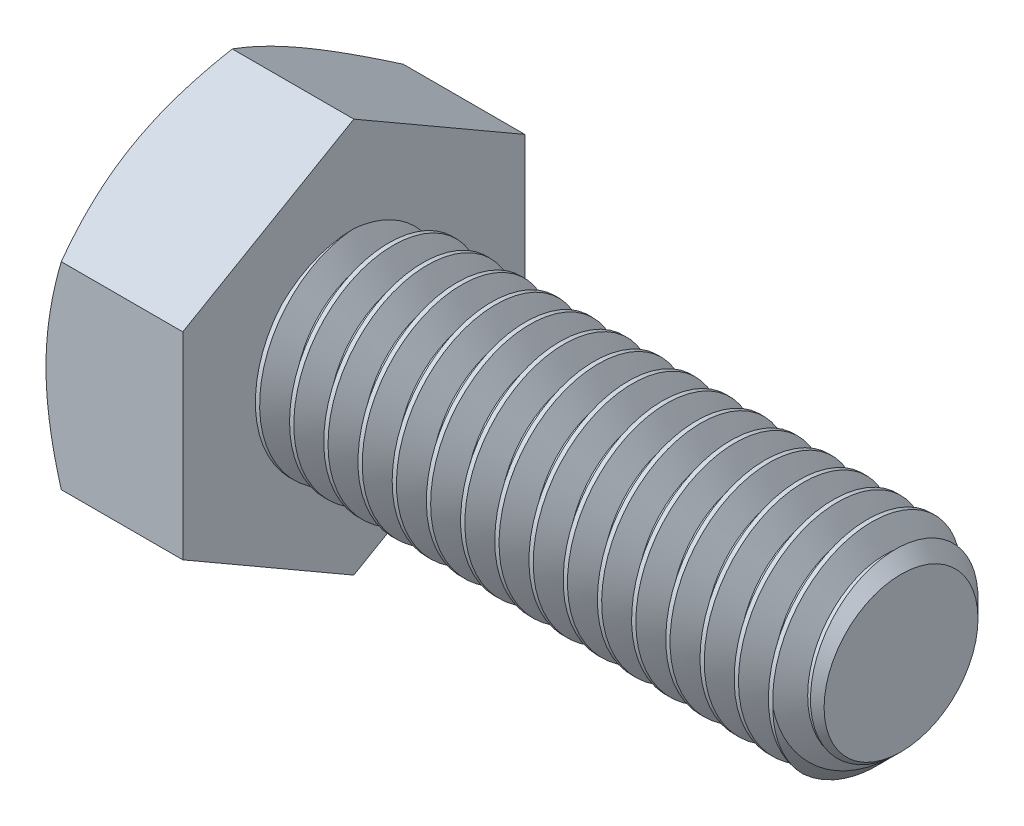
SolidWorks part; units mm, degrees
ref_plane "Front Plane" through (0, 0, 0) normal (0, 0, 1) x (1, 0, 0)
ref_plane "Top Plane" through (0, 0, 0) normal (0, 1, 0) x (1, 0, 0)
ref_plane "Right Plane" through (0, 0, 0) normal (1, 0, 0) x (0, 0, -1)
sketch "Sketch1" plane through (0, 0, 0) normal (0, 0, 1) x (1, 0, 0)
  line L0 (-10, 0) -> (10, 0) construction
  line L1 (-6, 5) -> (-6, -5) construction
  line L2 (-10, 5) -> (-10, -5) construction
  line L3 (10, 3) -> (10, -3) construction
  point P8 (6.5, -3)
  dimension "D1" = 3.5
  dimension "Thread Dia" = 6
  dimension "Hex" = 10
  dimension "Head Ht" = 4
  dimension "Length" = 16
ref_plane "Plane2" through (10, 0, 0) normal (1, 0, 0) x (0, 0, -1)
sketch "Sketch2" plane through (10, 0, 0) normal (1, 0, 0) x (0, 0, -1)
  circle A0 centre (0, 0) radius 3
extrude "Boss-Extrude1" add sketch "Sketch2" against normal up to vertex (16 mm away) up to point (-6, -5, 0)
sketch "Sketch4" plane through (10, 0, 0) normal (1, 0, 0) x (0, 0, -1)
  circle A1 centre (0, 0) radius 3
  circle A2 centre (0, 0) radius 3
  dimension "D1" = 0
curve "Helix/Spiral1" pitch 1 height 17 turns 17 parameters "Pitch"=1
chamfer "Chamfer1" distance 0.75 angle 45 1 edges at (10, 0, -3)
sketch "Sketch5" plane through (0, 0, 0) normal (0, 0, 1) x (1, 0, 0)
  line L0 (10, 3) -> (10.375, 2.3505)
  line L1 (10.375, 2.3505) -> (10.5, 2.3505)
  line L2 (10.5, 2.3505) -> (10.875, 3)
  line L3 (10, 3) -> (10.875, 3)
  line L4 (10.4375, 2.3505) -> (10.4375, 3) construction
  line L5 (10.1875, 2.6752) -> (10.6875, 2.6752) construction
  line L6 (10, -3) -> (10, 3) construction
  dimension "D1" = 60
  dimension "D2" = 0.125
  dimension "D3" = 0.5
sweep "Cut-Sweep1" cut profiles "Sketch5" path "Helix/Spiral1" align with end faces yes
sketch "Sketch3" plane through (-6, 0, 0) normal (-1, 0, 0) x (0, 0, 1)
  line L0 (0, 5) -> (0, -5) construction
  line L1 (-5, -2.8868) -> (0, -5.7735)
  line L2 (0, -5.7735) -> (5, -2.8868)
  line L3 (5, -2.8868) -> (5, 2.8868)
  line L4 (5, 2.8868) -> (0, 5.7735)
  line L5 (0, 5.7735) -> (-5, 2.8868)
  line L6 (-5, 2.8868) -> (-5, -2.8868)
  circle A0 centre (0, 0) radius 5 construction
extrude "Boss-Extrude2" add sketch "Sketch3" along normal up to vertex (4 mm away) up to point (-10, -5, 0)
sketch "Sketch6" plane through (-10, 0, 0) normal (-1, 0, 0) x (0, 0, 1)
  circle A0 centre (0, 0) radius 5 construction
  circle A1 centre (0, 0) radius 5
extrude "Cut-Extrude1" cut sketch "Sketch6" against normal through all draft 60 flip side to cut
sketch "Sketch9" plane through (0, 0, 0) normal (0, 0, 1) x (1, 0, 0)
  line L0 (-6, 3) -> (-6, 0)
  line L1 (-6, 0) -> (-41, 0)
  line L2 (-41, 0) -> (-44, 3)
  line L3 (-44, 3) -> (-6, 3)
  line L4 (-10, 0) -> (10, 0) construction
  line L5 (-6, 5) -> (-6, -5) construction
  line L6 (10, 3) -> (10, -3) construction
  dimension "D1" = 45
  dimension "MinThreadLg" = 54
revolve "Revolve1" [suppressed] add sketch "Sketch9" angle 360 about L1
equation "\"D2@Sketch5\" = \"Pitch@Helix/Spiral1\"*.125"
equation "\"D3@Sketch5\" = \"Pitch@Helix/Spiral1\"*.50"
equation "\"D3@Helix/Spiral1\" = \"Length@Sketch1\"+\"Pitch@Helix/Spiral1\""
equation "\"D1@Chamfer1\" = \"Pitch@Helix/Spiral1\"*.750"
equation "\"D1@Sketch1\" = \"Pitch@Helix/Spiral1\"*3.50"
